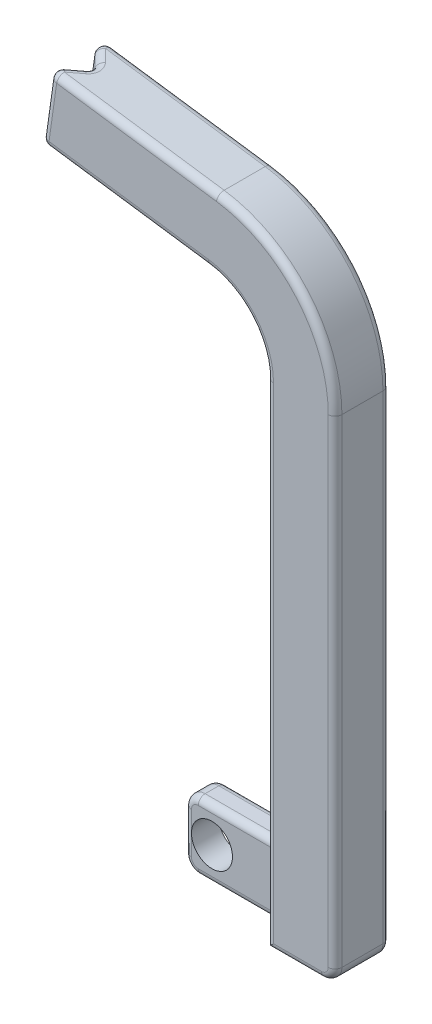
SolidWorks part; units mm, degrees
ref_plane "前视基准面" through (0, 0, 0) normal (0, 0, 1) x (1, 0, 0)
ref_plane "上视基准面" through (0, 0, 0) normal (0, 1, 0) x (1, 0, 0)
ref_plane "右视基准面" through (0, 0, 0) normal (1, 0, 0) x (0, 0, -1)
sketch "草图1" plane through (0, 0, 0) normal (0, 0, 1) x (1, 0, 0)
  line L1 (-5.5, 2.5) -> (5.5, 2.5)
  line L2 (-6.5, 1.5) -> (-6.5, -1.5)
  line L3 (-5.5, -2.5) -> (5.5, -2.5)
  line L4 (6.5, 1.5) -> (6.5, -1.5)
  line L5 (-6.5, 2.5) -> (6.5, -2.5) construction
  line L6 (-6.5, -2.5) -> (6.5, 2.5) construction
  arc A0 (5.5, 2.5) -> (6.5, 1.5) centre (5.5, 1.5) cw
  arc A1 (5.5, -2.5) -> (6.5, -1.5) centre (5.5, -1.5) ccw
  arc A2 (-6.5, -1.5) -> (-5.5, -2.5) centre (-5.5, -1.5) ccw
  arc A3 (-5.5, 2.5) -> (-6.5, 1.5) centre (-5.5, 1.5) ccw
  point P0 (0, 0)
  dimension "D3" = 1
  dimension "D1" = 13
  dimension "D2" = 5
extrude "凸台-拉伸1" add sketch "草图1" along normal blind 2
sketch "草图2" plane through (0, 0, 2) normal (0, 0, 1) x (1, 0, 0)
  line L0 (6.5, 1.5) -> (6.5, 33.5)
  line L1 (-2.1083, 43.4027) -> (-14.9818, 45.2119)
  line L2 (1.5, 2.5) -> (1.5, 33.5)
  line L3 (-2.8041, 38.4513) -> (-15.6776, 40.2606)
  line L4 (-14.9818, 45.2119) -> (-15.6776, 40.2606)
  line L8 (1.5, 1.5) -> (1.5, 33.5) construction
  line L9 (-2.8041, 38.4513) -> (-15.5872, 38.4513) construction
  line L10 (-5.5, -2.5) -> (5.5, -2.5) construction
  line L11 (6.5, -1.5) -> (6.5, 1.5) construction
  line L12 (1.5, -2.5) -> (5.5, -2.5)
  line L13 (6.5, -1.5) -> (6.5, 1.5)
  line L14 (1.5, 2.5) -> (1.5, -2.5)
  arc A0 (6.5, 33.5) -> (-2.1083, 43.4027) centre (-3.5, 33.5) ccw
  arc A1 (1.5, 33.5) -> (-2.8041, 38.4513) centre (-3.5, 33.5) ccw
  arc A4 (5.5, -2.5) -> (6.5, -1.5) centre (5.5, -1.5) ccw construction
  arc A5 (5.5, -2.5) -> (6.5, -1.5) centre (5.5, -1.5) ccw
  dimension "D3" = 10
  dimension "D1" = 13
  dimension "D2" = 32
  dimension "D4" = 5
  dimension "D5" = 8
extrude "凸台-拉伸2" add sketch "草图2" along normal mid plane 4
sketch "草图3" plane through (5.9409, 42.2714, 0) normal (0.1392, 0.9903, 0) x (0.9903, -0.1392, 0)
  line L0 (-21.1282, 0) -> (-19.126, -2)
  line L1 (-8.1282, 0) -> (-21.1282, 0) construction
  line L2 (-21.1282, -4) -> (-21.1282, 0) construction
  line L3 (-19.126, -2) -> (-21.1282, -4)
  line L4 (-21.1282, 0) -> (-21.1282, -4)
  dimension "D1" = 2.83
  dimension "D2" = 2.83
extrude "切除-拉伸1" cut sketch "草图3" against normal up to surface (5 mm away) up to face at (-9.2409, 39.356, 2)
sketch "草图4" plane through (0, 0, 2) normal (0, 0, 1) x (1, 0, 0)
  line L0 (-6.5, 1.5) -> (-6.5, -1.5) construction
  circle A0 centre (-4.5, 0) radius 1.5
  dimension "D3" = 3
  dimension "D1" = 2
extrude "切除-拉伸2" cut sketch "草图4" against normal through all
fillet "圆角1" radius 0.5 32 edges at (-14.6863, 40.1213, 3) (-13.9904, 45.0726, 3) (3.5, -2.5, 4) (6.2071, -2.2071, 4) (6.5, 16, 4) (4.0471, 40.0606, 4) (-9.2409, 39.356, 0) (1.5, 18, 0) (-8.545, 44.3073, 0) (4.0471, 40.0606, 0) (6.5, 16, 0) (6.2071, -2.2071, 0) (0, -2.5, 0) (-6.2071, -2.2071, 0) (-6.5, 0, 0) (-6.2071, 2.2071, 0) (-2, -2.5, 2) (-6.2071, -2.2071, 2) (-6.5, 0, 2) (-6.2071, 2.2071, 2) (-9.2409, 39.356, 4) (0.2735, 36.7803, 4) (-14.6863, 40.1213, 1) (-15.3297, 42.7363, 4) (-13.9904, 45.0726, 1) (-13.3469, 42.4576, 2) (-15.3297, 42.7363, 0) (-8.545, 44.3073, 4) (0.2735, 36.7803, 0) (-2, 2.5, 0) (-2, 2.5, 2) (1.5, 15.5, 4)
